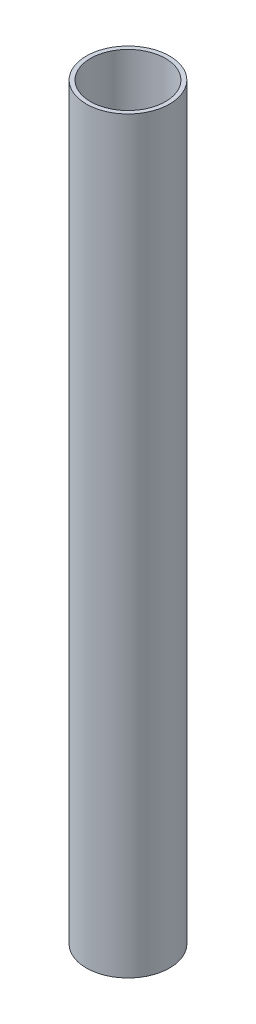
SolidWorks part; units mm, degrees
material "Toray T700"
ref_plane "Front" through (0, 0, 0) normal (0, 0, 1) x (1, 0, 0)
ref_plane "Top" through (0, 0, 0) normal (0, 1, 0) x (1, 0, 0)
ref_plane "Right" through (0, 0, 0) normal (1, 0, 0) x (0, 0, -1)
sketch "Sketch1" plane through (0, 0, 0) normal (0, 1, 0) x (1, 0, 0)
  line L5 (4.7969, 0) -> (-5.97, 0) construction
  circle A0 centre (0, 0) radius 10
  circle A1 centre (0, 0) radius 9
  dimension "D1" = 20
  dimension "D2" = 18
extrude "Boss-Extrude1" add sketch "Sketch1" along normal blind 179.7
